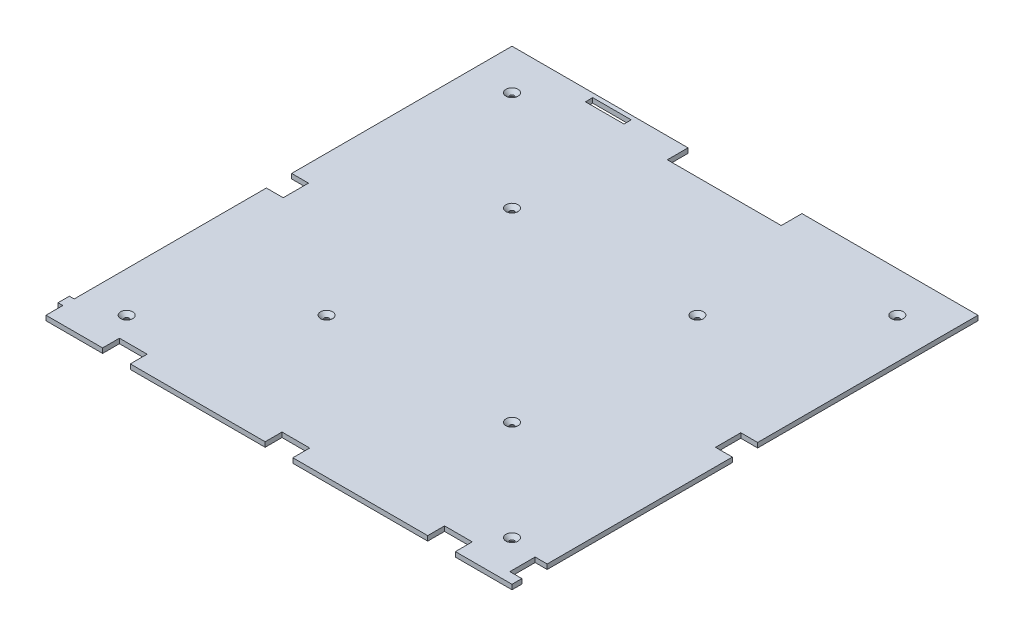
SolidWorks part; units mm, degrees
ref_plane "Front Plane" through (0, 0, 0) normal (0, 0, 1) x (1, 0, 0)
ref_plane "Top Plane" through (0, 0, 0) normal (0, 1, 0) x (1, 0, 0)
ref_plane "Right Plane" through (0, 0, 0) normal (1, 0, 0) x (0, 0, -1)
sketch "Sketch1" plane through (0, 0, 0) normal (0, 1, 0) x (1, 0, 0)
  line L0 (5.5, -97) -> (61.9965, -97) construction
  line L1 (5.5, -90.0036) -> (5.5, -97) construction
  line L2 (-5.5, -90.0036) -> (5.5, -90.0036) construction
  line L3 (-5.5, -97) -> (-5.5, -90.0036) construction
  line L4 (-61.9965, -97) -> (-5.5, -97) construction
  line L5 (-61.9965, -90.0036) -> (-61.9965, -97) construction
  line L6 (-72.9965, -90.0036) -> (-61.9965, -90.0036) construction
  line L7 (-72.9965, -97) -> (-72.9965, -90.0036) construction
  line L8 (-97, -97) -> (-72.9965, -97) construction
  line L9 (-97, -90) -> (-97, -97) construction
  line L10 (-99, -90) -> (-97, -90) construction
  line L11 (-99, -84.8) -> (-99, -90) construction
  line L12 (-97, -84.8) -> (-99, -84.8) construction
  line L13 (-97, 97) -> (-97, -84.8) construction
  line L14 (-23.4, 97) -> (-97, 97) construction
  line L15 (-23.4, 88.4) -> (-23.4, 97) construction
  line L16 (23.4, 88.4) -> (-23.4, 88.4) construction
  line L17 (23.4, 97) -> (23.4, 88.4) construction
  line L18 (97, 97) -> (23.4, 97) construction
  line L19 (97, -82.4) -> (97, 97) construction
  line L20 (92, -82.4) -> (97, -82.4) construction
  line L21 (92, -92.4) -> (92, -82.4) construction
  line L22 (97, -92.4) -> (92, -92.4) construction
  line L23 (97, -97) -> (97, -92.4) construction
  line L24 (72.9965, -97) -> (97, -97) construction
  line L25 (72.9965, -90.0036) -> (72.9965, -97) construction
  line L26 (61.9965, -90.0036) -> (72.9965, -90.0036) construction
  line L27 (61.9965, -97) -> (61.9965, -90.0036) construction
  line L28 (5.75, -96.75) -> (61.7465, -96.75)
  line L29 (61.7465, -96.75) -> (61.7465, -89.7536)
  line L30 (61.7465, -89.7536) -> (73.2465, -89.7536)
  line L31 (73.2465, -89.7536) -> (73.2465, -96.75)
  line L32 (73.2465, -96.75) -> (96.75, -96.75)
  line L33 (96.75, -96.75) -> (96.75, -92.65)
  line L34 (96.75, -92.65) -> (91.75, -92.65)
  line L35 (91.75, -92.65) -> (91.75, -82.15)
  line L36 (91.75, -82.15) -> (96.75, -82.15)
  line L37 (96.75, -82.15) -> (96.75, 96.75)
  line L38 (96.75, 96.75) -> (23.65, 96.75)
  line L39 (23.65, 96.75) -> (23.65, 88.15)
  line L40 (23.65, 88.15) -> (-23.65, 88.15)
  line L41 (-23.65, 88.15) -> (-23.65, 96.75)
  line L42 (-23.65, 96.75) -> (-96.75, 96.75)
  line L43 (-96.75, 96.75) -> (-96.75, -85.05)
  line L44 (-96.75, -85.05) -> (-98.75, -85.05)
  line L45 (-98.75, -85.05) -> (-98.75, -89.75)
  line L46 (-98.75, -89.75) -> (-96.75, -89.75)
  line L47 (-96.75, -89.75) -> (-96.75, -96.75)
  line L48 (-96.75, -96.75) -> (-73.2465, -96.75)
  line L49 (-73.2465, -96.75) -> (-73.2465, -89.7536)
  line L50 (-73.2465, -89.7536) -> (-61.7465, -89.7536)
  line L51 (-61.7465, -89.7536) -> (-61.7465, -96.75)
  line L52 (-61.7465, -96.75) -> (-5.75, -96.75)
  line L53 (-5.75, -96.75) -> (-5.75, -89.7536)
  line L54 (-5.75, -89.7536) -> (5.75, -89.7536)
  line L55 (5.75, -89.7536) -> (5.75, -96.75)
  dimension "D1" = 194
  dimension "D2" = 8.6
  dimension "D3" = 194
  dimension "D4" = 73.6
  dimension "D5" = 46.8
  dimension "D6" = 5
  dimension "D7" = 4.6
  dimension "D8" = 10
  dimension "D9" = 6.9964
  dimension "D10" = 24.0035
  dimension "D11" = 11
  dimension "D12" = 56.4965
  dimension "D13" = 56.4965
  dimension "D14" = 7
  dimension "D15" = 2
  dimension "D16" = 5.2
  dimension "D17" = 97
  dimension "D18" = 97
  dimension "D19" = 0.25
extrude "Boss-Extrude1" add sketch "Sketch1" along normal blind 2
sketch "Sketch2" plane through (0, 0, 0) normal (0, -1, 0) x (1, 0, 0)
  circle A0 centre (80, 80) radius 1
  circle A1 centre (-80, 80) radius 1
  circle A2 centre (-38.5, 38.5) radius 1
  circle A3 centre (38.5, 38.5) radius 1
  circle A4 centre (80, -80) radius 1
  circle A5 centre (-80, -80) radius 1
  circle A6 centre (38.5, -38.5) radius 1
  circle A7 centre (-38.5, -38.5) radius 1
  dimension "D1" = 2
  dimension "D2" = 2
  dimension "D3" = 2
  dimension "D4" = 2
  dimension "D5" = 2
  dimension "D6" = 2
  dimension "D7" = 2
  dimension "D8" = 2
extrude "Cut-Extrude1" cut sketch "Sketch2" against normal through all both and the other way through all
chamfer "Chamfer1" distance 1.5 angle 45 8 edges at (80, 2, 79) (-80, 2, 79) (38.5, 2, 37.5) (-38.5, 2, 37.5) (-38.5, 2, -39.5) (80, 2, -81) (38.5, 2, -39.5) (-80, 2, -81)
sketch "Sketch3" plane through (0, 0, 0) normal (0, -1, 0) x (1, 0, 0)
  line L0 (-23.65, -96.75) -> (-96.75, -96.75) construction
  line L1 (-43.75, -20.75) -> (-33.75, -20.75)
  line L2 (-43.75, -20.75) -> (-43.75, 20.25)
  line L3 (-43.75, 20.25) -> (-33.75, 20.25)
  line L4 (-33.75, -20.75) -> (-33.75, 20.25)
  line L5 (-96.75, -96.75) -> (-96.75, 85.05) construction
  dimension "D1" = 41
  dimension "D2" = 76
  dimension "D3" = 53
  dimension "D4" = 10
extrude "Cut-Extrude2" cut sketch "Sketch3" against normal blind 1.4
sketch "Sketch4" plane through (0, 2, 0) normal (0, 1, 0) x (1, 0, 0)
  line L0 (-96.75, 96.75) -> (-96.75, -85.05) construction
  line L1 (-96.75, 5.25) -> (-89.75, 5.25)
  line L2 (-96.75, 5.25) -> (-96.75, -5.25)
  line L3 (-96.75, -5.25) -> (-89.75, -5.25)
  line L4 (-89.75, 5.25) -> (-89.75, -5.25)
  line L5 (96.75, -82.15) -> (96.75, 96.75) construction
  line L6 (96.75, 5.25) -> (89.75, 5.25)
  line L7 (96.75, 5.25) -> (96.75, -5.25)
  line L8 (96.75, -5.25) -> (89.75, -5.25)
  line L9 (89.75, 5.25) -> (89.75, -5.25)
  line L10 (97, 5) -> (90, 5) construction
  line L11 (90, 5) -> (90, -5) construction
  line L12 (97, -5) -> (90, -5) construction
  line L13 (-97, 5) -> (-90, 5) construction
  line L14 (-97, -5) -> (-90, -5) construction
  line L15 (-90, 5) -> (-90, -5) construction
  dimension "D1" = 0.25
  dimension "D2" = 0.25
  dimension "D3" = 0.25
  dimension "D4" = 0.25
  dimension "D5" = 0.25
  dimension "D6" = 0.25
extrude "Cut-Extrude3" cut sketch "Sketch4" against normal through all
sketch "Sketch5" plane through (0, 0, 0) normal (0, -1, 0) x (1, 0, 0)
  line L1 (-45.5, -95) -> (-61.5, -95)
  line L2 (-45.5, -95) -> (-45.5, -92)
  line L3 (-45.5, -92) -> (-61.5, -92)
  line L4 (-61.5, -95) -> (-61.5, -92)
extrude "Cut-Extrude4" cut sketch "Sketch5" against normal through all
